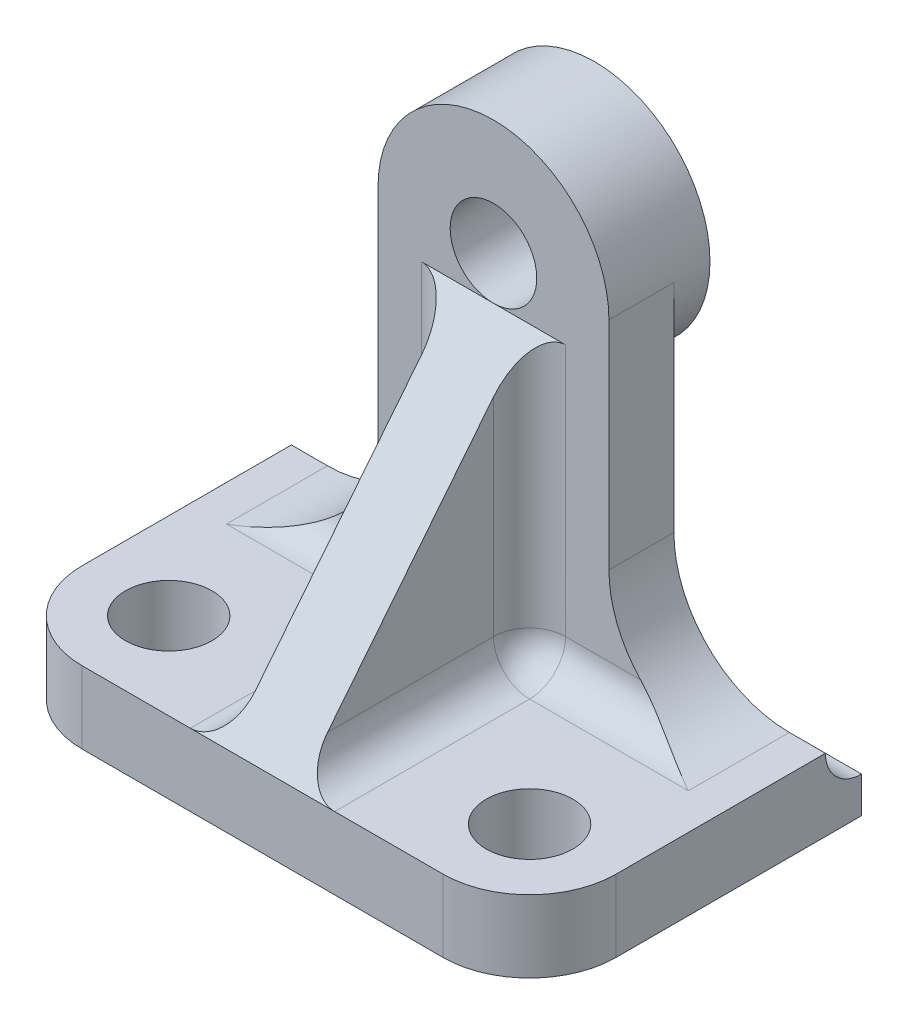
SolidWorks part; units mm, degrees
material "Gray Cast Iron"
ref_plane "Front Plane" through (0, 0, 0) normal (0, 0, 1) x (1, 0, 0)
ref_plane "Top Plane" through (0, 0, 0) normal (0, 1, 0) x (1, 0, 0)
ref_plane "Right Plane" through (0, 0, 0) normal (1, 0, 0) x (0, 0, -1)
sketch "Sketch8" plane through (0, 0, 0) normal (0, 0, 1) x (1, 0, 0)
  line L1 (-32.7822, 0) -> (41.2178, 0)
  line L2 (-32.7822, 0) -> (-32.7822, -10)
  line L3 (-32.7822, -10) -> (41.2178, -10)
  line L4 (41.2178, 0) -> (41.2178, -10)
  dimension "D1" = 74
  dimension "D2" = 10
extrude "Boss-Extrude9" add sketch "Sketch8" along normal blind 46 contours L1 L4 L3 L2
fillet "Fillet8" radius 12 1 edges at (-32.7822, -5, 46)
fillet "Fillet9" radius 12 1 edges at (41.2178, -5, 46)
sketch "Sketch10" plane through (-32.7822, 0, 0) normal (-1, 0, 0) x (0, 0, 1)
  line L0 (34, 0) -> (0, 0) construction
  line L1 (0, 0) -> (0, -10) construction
  arc A0 (5, 0) -> (0, -5) centre (0, 0) cw
  dimension "D1" = 5
extrude "Cut-Extrude3" cut sketch "Sketch10" against normal through all and the other way through all flip side to cut
ref_plane "Plane2" through (4.2178, 0, 0) normal (-1, 0, 0) x (0, 0, 1)
sketch "Sketch13" plane through (0, 0, 0) normal (0, 0, 1) x (1, 0, 0)
  line L1 (-32.7822, 0) -> (41.2178, 0) construction
  line L2 (-11.7822, 0) -> (20.2178, 0)
  line L3 (-11.7822, 0) -> (-11.7822, 46)
  line L5 (20.2178, 0) -> (20.2178, 46)
  line L6 (4.2178, 46.9442) -> (4.2178, -46.9442) construction
  arc A0 (-11.7822, 46) -> (20.2178, 46) centre (4.2178, 46) cw
  circle A1 centre (4.2178, 46) radius 6
  dimension "D2" = 16
  dimension "D3" = 12
  dimension "D1" = 46
extrude "Boss-Extrude10" add sketch "Sketch13" along normal blind 14
sketch "Sketch15" plane through (-11.7822, 0, 0) normal (-1, 0, 0) x (0, 0, 1)
  line L0 (0, 46) -> (0, 0) construction
  line L1 (0, 46) -> (5, 46)
  line L2 (0, 46) -> (0, 0)
  line L3 (0, 0) -> (5, 0)
  line L4 (5, 46) -> (5, 0)
  line L5 (14, 46) -> (0, 46) construction
extrude "Cut-Extrude4" cut sketch "Sketch15" against normal up to next
sketch "Sketch26" plane through (0, 0, 0) normal (0, 0, -1) x (-1, 0, 0)
  circle A0 centre (-4.2178, 46) radius 16
extrude "Boss-Extrude11" add sketch "Sketch26" against normal blind 14
sketch "Sketch27" plane through (0, 0, 0) normal (0, 0, -1) x (-1, 0, 0)
  line L0 (-4.2178, 62) -> (-4.2178, 30) construction
  line L1 (-20.2178, 46) -> (11.7822, 46) construction
  circle A3 centre (-4.2178, 46) radius 16 construction
fillet "Fillet11" radius 5 1 edges at (4.2178, 0, 14)
fillet "Fillet12" radius 16 2 edges at (-11.7822, 0, 12) (20.2178, 0, 12)
sketch "Sketch28" plane through (0, 0, 0) normal (0, 0, -1) x (-1, 0, 0)
  line L0 (-4.2178, 62) -> (-4.2178, 30) construction
  circle A0 centre (-4.2178, 46) radius 6
  dimension "D1" = 12
extrude "Cut-Extrude5" cut sketch "Sketch28" against normal through all
sketch "Sketch31" plane through (4.2178, 0, 0) normal (-1, 0, 0) x (0, 0, 1)
  line L0 (14, 40) -> (46, 0)
rib "Rib2" sketch "Sketch31" sketch "Sketch31" thickness 10 extrusion direction parallel to sketch draft on no parameters "D1"=10
fillet "Fillet13" radius 5 6 edges at (9.2178, 22.5, 14) (9.2178, 1.4645, 15.4645) (-0.7822, 22.5, 14) (-0.7822, 1.4645, 15.4645) (9.2178, 0, 32.5) (-0.7822, 0, 32.5)
sketch "Sketch36" plane through (0, 0, 0) normal (0, 1, 0) x (1, 0, 0)
  line L0 (-20.7822, -34) -> (29.2178, -34) construction
  line L1 (-20.7822, -19.8724) -> (-20.7822, -51.3013) construction
  line L2 (29.2178, -19) -> (29.2178, -60.5263) construction
  line L3 (36.2178, -19) -> (14.2178, -19) construction
  circle A0 centre (-20.7822, -34) radius 6
  circle A1 centre (29.2178, -34) radius 6
  arc A4 (-32.7822, -34) -> (-20.7822, -46) centre (-20.7822, -34) ccw construction
  arc A6 (29.2178, -46) -> (41.2178, -34) centre (29.2178, -34) ccw construction
  point P14 (-29.2675, -42.4853)
  point P19 (37.7031, -42.4853)
  dimension "D2" = 12
  dimension "D3" = 12
  dimension "D4" = 12
  dimension "D1" = 12
  dimension "D5" = 50
  dimension "D6" = 50
extrude "Cut-Extrude6" cut sketch "Sketch36" against normal through all
